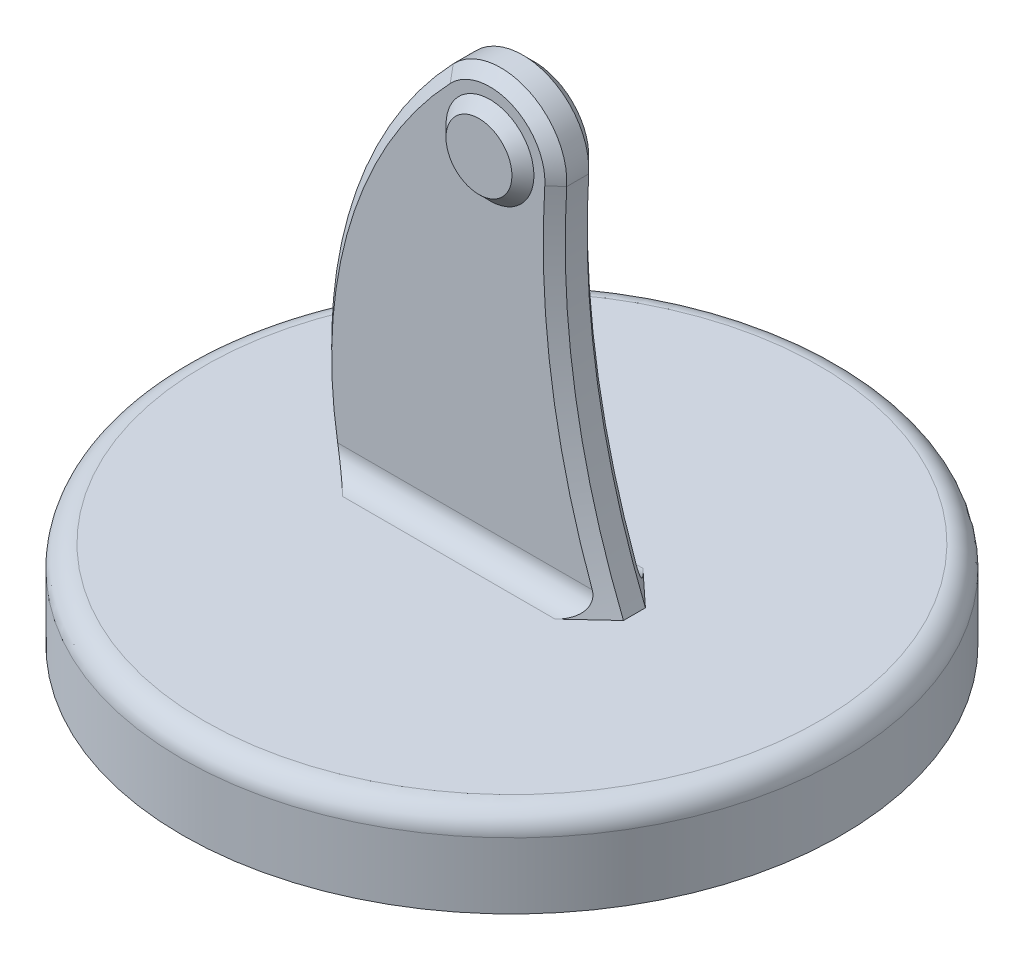
SolidWorks part; units mm, degrees
ref_plane "Front Plane" through (0, 0, 0) normal (0, 0, 1) x (1, 0, 0)
ref_plane "Top Plane" through (0, 0, 0) normal (0, 1, 0) x (1, 0, 0)
ref_plane "Right Plane" through (0, 0, 0) normal (1, 0, 0) x (0, 0, -1)
sketch "Sketch2" plane through (0, 0, 0) normal (0, 1, 0) x (1, 0, 0)
  circle A0 centre (0, 0) radius 75
  dimension "D1" = 150
extrude "Boss-Extrude1" add sketch "Sketch2" along normal blind 20
fillet "Fillet1" radius 5 1 edges at (0, 20, 75)
sketch "Sketch3" plane through (0, 0, 0) normal (0, 0, 1) x (1, 0, 0)
  line L0 (0, -1.704) -> (0, 100) construction
  line L1 (-75, 15) -> (75, 15) construction
  line L2 (-35, 15) -> (30, 15)
  arc A0 (14.9706, 99.062) -> (-10.8492, 110.3583) centre (0, 100) ccw
  arc A1 (-35, 15) -> (-10.8492, 110.3583) centre (61.4788, 41.3028) cw
  arc A2 (14.9706, 99.062) -> (30, 15) centre (194.6184, 87.8065) ccw
  dimension "D1" = 30
  dimension "D4" = 30
  dimension "D5" = 180
  dimension "D6" = 100
  dimension "D2" = 35
  dimension "D3" = 100
extrude "Boss-Extrude2" add sketch "Sketch3" along normal mid plane 10
chamfer "Chamfer4" distance 2.5 angle 45 6 edges at (16.9703, 58.8038, 5) (-34.7965, 68.3412, 5) (6.0123, 113.7423, 5) (16.9703, 58.8038, -5) (6.0123, 113.7423, -5) (-34.7965, 68.3412, -5)
fillet "Fillet2" radius 5 2 edges at (-4.2415, 20, 5) (-4.2415, 20, -5)
sketch "Sketch7" plane through (0, 0, 5) normal (0, 0, 1) x (1, 0, 0)
  circle A0 centre (0, 100) radius 10
  dimension "D1" = 20
extrude "Boss-Extrude3" add sketch "Sketch7" along normal mid plane 5
chamfer "Chamfer5" distance 2.5 angle 45 1 edges at (10, 100, 7.5)
sketch "Sketch8" plane through (0, 0, -5) normal (0, 0, -1) x (-1, 0, 0)
  circle A0 centre (0, 100) radius 5
  dimension "D1" = 10
extrude "Cut-Extrude1" cut sketch "Sketch8" against normal blind 10
